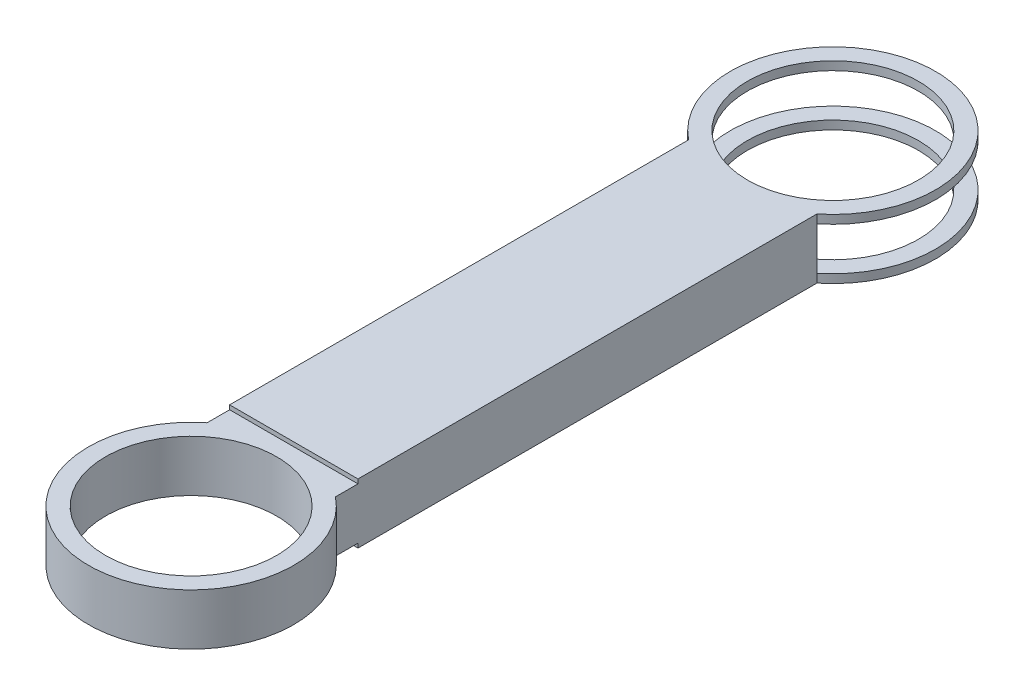
SolidWorks part; units mm, degrees
ref_plane "Front Plane" through (0, 0, 0) normal (0, 0, 1) x (1, 0, 0)
ref_plane "Top Plane" through (0, 0, 0) normal (0, 1, 0) x (1, 0, 0)
ref_plane "Right Plane" through (0, 0, 0) normal (1, 0, 0) x (0, 0, -1)
sketch "Profile Sketch" plane through (0, 0, 0) normal (0, 1, 0) x (1, 0, 0)
  line L0 (-7.5, 28.1325) -> (-7.5, -28.1325)
  line L1 (7.5, 28.1325) -> (7.5, -28.1325)
  line L2 (-7.5, 0) -> (7.5, 0) construction
  circle A0 centre (0, -37.5) radius 10
  circle A1 centre (0, 37.5) radius 10
  arc A2 (7.5, 28.1325) -> (-7.5, 28.1325) centre (0, 37.5) ccw
  arc A3 (-7.5, -28.1325) -> (7.5, -28.1325) centre (0, -37.5) ccw
  point P9 (-7.5, 0)
  point P12 (7.5, 0)
  point P13 (0, 0)
  dimension "D1" = 20
  dimension "D2" = 2
  dimension "D3" = 75
  dimension "D4" = 15
extrude "Profile Extrude" add sketch "Profile Sketch" along normal blind 7
sketch "Wrist Cut Sketch" plane through (0, 0, 0) normal (0, 1, 0) x (1, 0, 0)
  line L0 (-7.5, -28.1325) -> (-7.5, -25.5)
  line L1 (-7.5, -25.5) -> (7.5, -25.5)
  line L2 (7.5, -25.5) -> (7.5, -28.1325)
  line L3 (7.5, -28.1325) -> (7.5, 28.1325) construction
  line L4 (-7.5, 28.1325) -> (-7.5, -28.1325) construction
  arc A0 (-7.5, -28.1325) -> (7.5, -28.1325) centre (0, -37.5) ccw
  arc A1 (-7.5, -28.1325) -> (7.5, -28.1325) centre (0, -37.5) ccw construction
  point P9 (0, 0)
  point P10 (0, 0)
  point P11 (0, 0)
extrude "Upper Wrist Cut" cut sketch "Wrist Cut Sketch" along normal blind 0.5 from surface starting at face at (0, 0, 0)
extrude "Lower Wrist Cut" cut sketch "Sketch2<2>" against normal blind 0.5 from surface starting at face at (0, 7, 47.5)
sketch "Sketch2<2>" plane through (0, 0, 0) normal (0, 1, 0) x (1, 0, 0) same geometry as "Wrist Cut Sketch"
sketch "Finger Cut Sketch" plane through (0, 0, 0) normal (1, 0, 0) x (0, 0, -1)
  line L1 (49.5, 1) -> (26.1325, 1)
  line L2 (49.5, 1) -> (49.5, 6)
  line L3 (49.5, 6) -> (26.1325, 6)
  line L4 (26.1325, 1) -> (26.1325, 6)
  line L5 (49.5, 1) -> (26.1325, 6) construction
  line L6 (49.5, 6) -> (26.1325, 1) construction
  line L8 (49.5, 0) -> (49.5, 7) construction
  line L9 (28.1325, 7) -> (28.1325, 0) construction
  line L10 (49.5, 7) -> (28.1325, 7) construction
  line L11 (28.1325, 0) -> (49.5, 0) construction
  point P0 (37.8163, 3.5)
  dimension "D1" = 2
  dimension "D2" = 1
  dimension "D3" = 1
extrude "Finger Cut" cut sketch "Finger Cut Sketch" against normal up to surface and the other way up to surface up to face at (0, 3.5, -38.8163) other way up to face at (0, 3.5, -38.8163)
